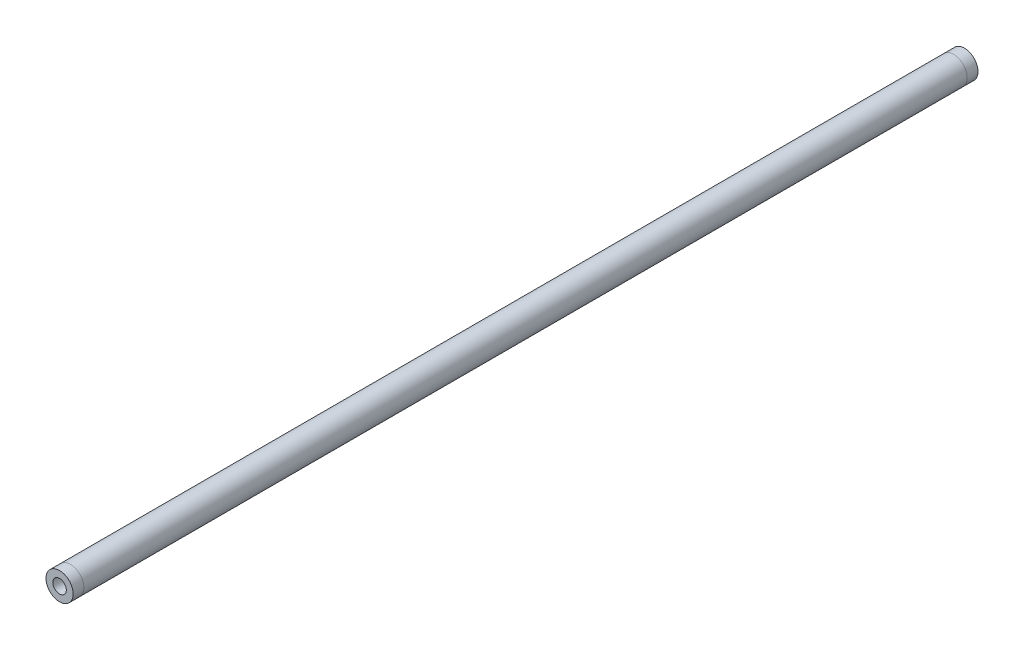
SolidWorks part; units mm, degrees
ref_plane "Front Plane" through (0, 0, 0) normal (0, 0, 1) x (1, 0, 0)
ref_plane "Top Plane" through (0, 0, 0) normal (0, 1, 0) x (1, 0, 0)
ref_plane "Right Plane" through (0, 0, 0) normal (1, 0, 0) x (0, 0, -1)
sketch "Axis" plane through (0, 0, 0) normal (1, 0, 0) x (0, 0, -1)
  line L0 (0, 0) -> (533.0363, 0) construction
  line L1 (533.0363, 0) -> (526.6863, 0)
  line L2 (533.0363, 0) -> (567.9613, 0) construction
  line L3 (0, 0) -> (-34.925, 0) construction
  point P4 (0, 0)
  point P5 (533.0363, 0)
  point P6 (526.6863, 0)
  point P8 (567.9613, 0)
  dimension "D1" = 6.35
  dimension "D2" = 34.925
  dimension "D3" = 34.925
sketch "Sketch1" plane through (0, 0, 0) normal (0, 0, 1) x (1, 0, 0)
  circle A0 centre (0, 0) radius 8.001
  circle A1 centre (0, 0) radius 6.477
  circle A2 centre (0, 0) radius 3.9688
  dimension "D1" = 16.002
  dimension "D2" = 1.524
  dimension "D3" = 7.9375
extrude "Threaded insert 1-1" add sketch "Sketch1" against normal blind 6.35 contours A0 A1 | A1 A2 region at (-7.7747, 0, 0) region at (-6.2938, 0, 0)
extrude "Threaded insert 1-2" add sketch "Sketch1<3>" against normal blind 9.525 from surface contours A1 A2 region at (-6.2938, 0, 0) starting at face at (8.001, 0, -6.35)
sketch "Sketch1<3>" plane through (0, 0, 0) normal (0, 0, 1) x (1, 0, 0) same geometry as "Sketch1"
extrude "Tube extrude" add sketch "Sketch1<4>" against normal up to vertex (526.6863 mm away) from surface separate body contours A0 A1 region at (-7.7747, 0, 0) up to point (0, 0, -526.6863) starting at face at (6.477, 0, -6.35)
sketch "Sketch1<4>" plane through (0, 0, 0) normal (0, 0, 1) x (1, 0, 0) same geometry as "Sketch1"
extrude "Threaded insert 2-1" add sketch "Sketch1<6>" along normal blind 9.525 from surface separate body contours A1 A2 region at (-6.2938, 0, 0) starting at face at (6.477, 0, -526.6863)
sketch "Sketch1<6>" plane through (0, 0, 0) normal (0, 0, 1) x (1, 0, 0) same geometry as "Sketch1"
extrude "Threaded insert 2-2" add sketch "Sketch1<9>" against normal blind 6.35 from surface separate body contours A1 A2 | A0 A1 region at (-7.7747, 0, 0) region at (-6.2938, 0, 0) starting at face at (6.477, 0, -526.6863)
sketch "Sketch1<9>" plane through (0, 0, 0) normal (0, 0, 1) x (1, 0, 0) same geometry as "Sketch1"
combine bodies "Combine1" operation type add bodies to combine 106 104
equation "\"Threaded insert outer thickness\"= .25"
equation "\"D1@Threaded insert 1-1\"=\"Threaded insert outer thickness\""
equation "\"D1@Threaded insert 2-2\"=\"Threaded insert outer thickness\""
equation "\"D1@Axis\" = \"Threaded insert outer thickness\""
